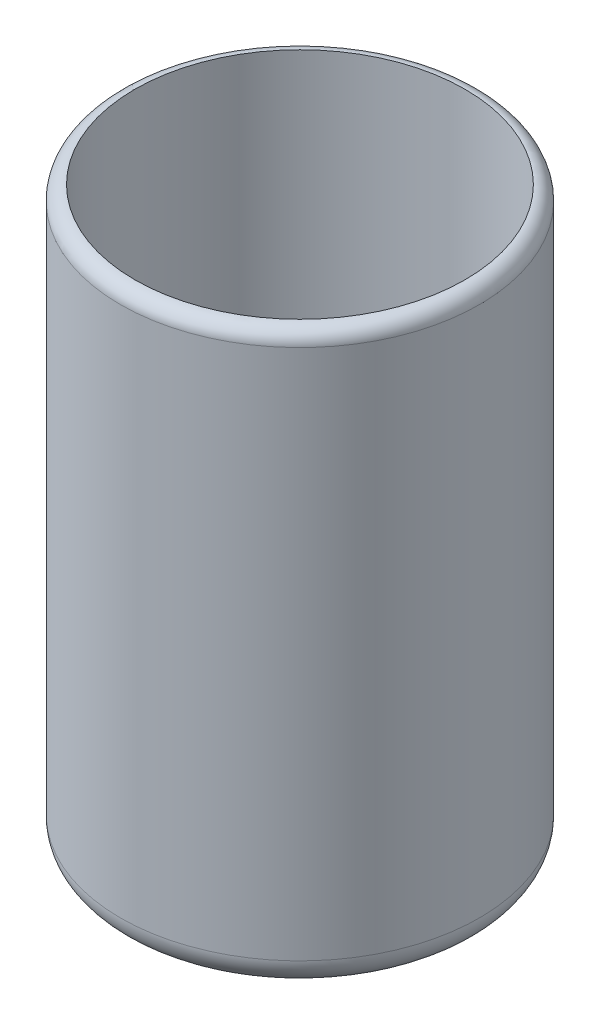
SolidWorks part; units mm, degrees
ref_plane "Front Plane" through (0, 0, 0) normal (0, 0, 1) x (1, 0, 0)
ref_plane "Top Plane" through (0, 0, 0) normal (0, 1, 0) x (1, 0, 0)
ref_plane "Right Plane" through (0, 0, 0) normal (1, 0, 0) x (0, 0, -1)
sketch "Sketch1" plane through (0, 0, 0) normal (0, 1, 0) x (1, 0, 0)
  circle A0 centre (0, 0) radius 12.5
  dimension "D1" = 25
extrude "Boss-Extrude1" add sketch "Sketch1" along normal blind 40
shell "Shell1" thickness 1 removed face at (0, 40, 12.5)
fillet "Fillet1" radius 2 1 edges at (0, 0, 12.5)
fillet "Fillet7" radius 1 1 edges at (0, 40, 12.5) type face fillet first side face at (0, 40, 11.5) second side face at (0, 2, 12.5)
